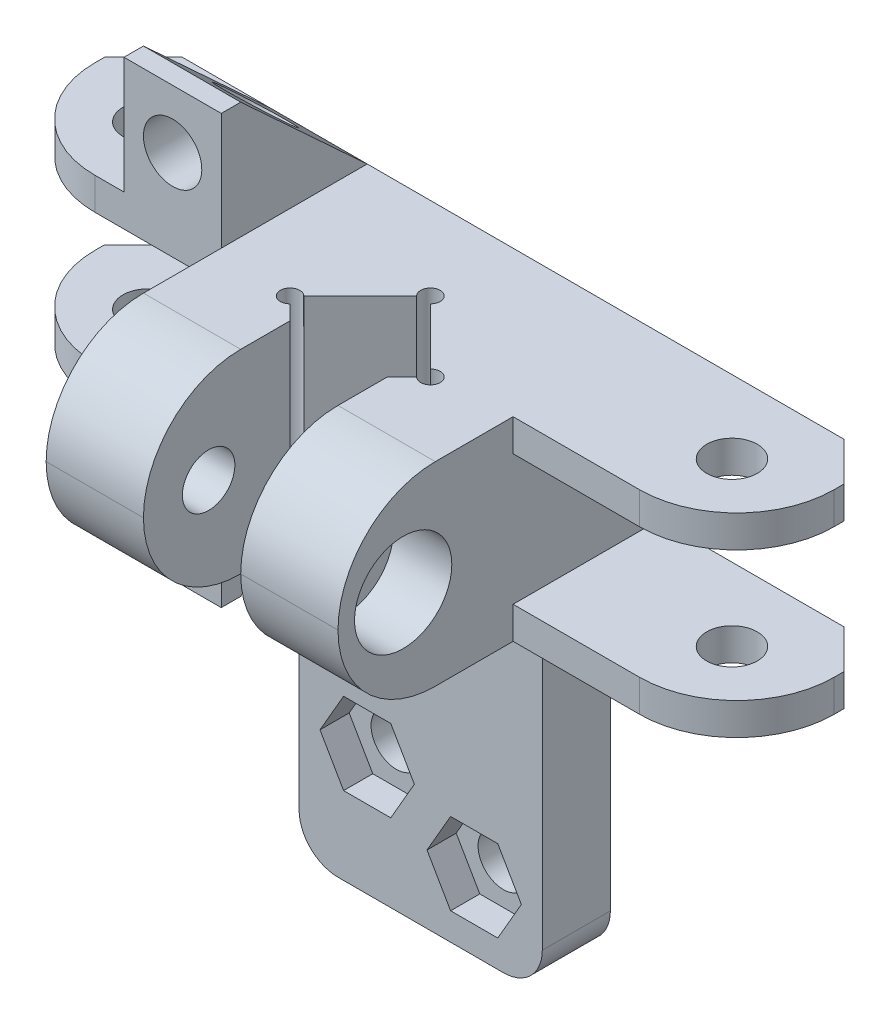
SolidWorks part; units mm, degrees
ref_plane "Ebene vorne" through (0, 0, 0) normal (0, 0, 1) x (1, 0, 0)
ref_plane "Ebene oben" through (0, 0, 0) normal (0, 1, 0) x (1, 0, 0)
ref_plane "Ebene rechts" through (0, 0, 0) normal (1, 0, 0) x (0, 0, -1)
sketch "Skizze1" plane through (0, 0, 0) normal (0, 1, 0) x (1, 0, 0)
  line L0 (-30, 5.945) -> (30, 5.945) construction
  line L1 (0, -6) -> (-30, -6) construction
  line L3 (46.7253, 15.715) -> (-46.7253, 15.715) construction
  line L4 (46.7253, 15.715) -> (46.7253, 35.715) construction
  line L5 (46.7253, 35.715) -> (-46.7253, 35.715) construction
  line L6 (-46.7253, 15.715) -> (-46.7253, 35.715) construction
  circle A0 centre (0, 0) radius 6 construction
  circle A1 centre (30, 5.945) radius 11.945 construction
  circle A2 centre (-30, 5.945) radius 11.945 construction
  circle A3 centre (0, 45.485) radius 11.945 construction
  point P7 (0, 5.945)
  point P14 (0, 15.715)
  point P17 (6, 0)
  point P18 (18.055, 5.945)
  dimension "D1" = 12
  dimension "D2" = 23.89
  dimension "D3" = 60
  dimension "D4" = 9.77
  dimension "D5" = 20
  dimension "D6" = 9.77
sketch "Skizze2" plane through (0, 0, 0) normal (0, 1, 0) x (1, 0, 0)
  line L0 (38, 13.445) -> (-38, 13.445)
  line L1 (-38, 13.445) -> (-38, -1.555)
  line L2 (-38, -1.555) -> (-15, -1.555)
  line L3 (-15, -1.555) -> (-15, -19.555)
  line L4 (-15, -19.555) -> (15, -19.555)
  line L5 (15, -19.555) -> (15, -1.555)
  line L6 (15, -1.555) -> (38, -1.555)
  line L7 (38, -1.555) -> (38, 13.445)
  line L8 (0, 13.445) -> (0, -19.555) construction
  line L9 (-30, 5.945) -> (30, 5.945) construction
  line L11 (0, -9.48) -> (7.2125, -2.2675)
  line L12 (0, -9.48) -> (-7.2125, -2.2675)
  line L13 (-7.2125, -2.2675) -> (0, 4.945)
  line L14 (7.2125, -2.2675) -> (0, 4.945)
  circle A0 centre (-30, 5.945) radius 2.6
  circle A1 centre (30, 5.945) radius 2.6
  circle A2 centre (0, 0) radius 6.1 construction
  circle A3 centre (0, 0) radius 6 construction
  point P21 (38, 5.945)
  dimension "D1" = 5.2
  dimension "D2" = 0.1
  dimension "D3" = 15
  dimension "D4" = 8
  dimension "D5" = 18
  dimension "D6" = 30
  dimension "D7" = 10.2
  dimension "D8" = 1
extrude "Aufsatz-Linear austragen1" add sketch "Skizze2" along normal mid plane 20
sketch "Skizze3" plane through (0, 0, 0) normal (0, 1, 0) x (1, 0, 0)
  line L1 (-5, -4.48) -> (5, -4.48)
  line L2 (-5, -4.48) -> (-5, -27.1109)
  line L3 (-5, -27.1109) -> (5, -27.1109)
  line L4 (5, -4.48) -> (5, -27.1109)
  line L5 (0, -9.48) -> (-7.2125, -2.2675) construction
  line L6 (0, -9.48) -> (7.2125, -2.2675) construction
  circle A0 centre (0, 4.945) radius 1
  circle A1 centre (-7.2125, -2.2675) radius 1
  circle A2 centre (7.2125, -2.2675) radius 1
  dimension "D2" = 2
  dimension "D1" = 10
extrude "Schnitt-Linear austragen1" cut sketch "Skizze3" against normal through all and the other way through all
sketch "Skizze4" plane through (0, 0, 0) normal (0, 0, 1) x (1, 0, 0)
  line L0 (42.3418, 0) -> (-42.3418, 0) construction
  line L1 (15, 6.7) -> (45, 6.7)
  line L2 (15, 6.7) -> (15, -6.7)
  line L3 (15, -6.7) -> (45, -6.7)
  line L4 (45, 6.7) -> (45, -6.7)
  line L5 (15, 10) -> (15, -10) construction
  point P4 (15, 0)
  point P7 (30, -6.7)
  dimension "D1" = 13.4
extrude "Schnitt-Linear austragen2" cut sketch "Skizze4" against normal through all and the other way through all
mirror "Spiegeln1" about plane through (0, 0, 0) normal (1, 0, 0) of "Schnitt-Linear austragen2"
sketch "Skizze5" plane through (0, 0, 0) normal (1, 0, 0) x (0, 0, -1)
  line L0 (42.3418, 0) -> (-42.3418, 0) construction
  line L1 (13.445, 0) -> (-19.555, 0) construction
  circle A0 centre (-12.855, 0) radius 2.7
  point P5 (-15.555, 0)
  dimension "D1" = 5.4
  dimension "D2" = 4
extrude "Schnitt-Linear austragen3" cut sketch "Skizze5" against normal through all and the other way through all
sketch "Skizze6" plane through (0, 0, 0) normal (1, 0, 0) x (0, 0, -1)
  circle A0 centre (-12.855, 0) radius 5
  dimension "D1" = 10
extrude "Schnitt-Linear austragen4" cut sketch "Skizze6" against normal blind 6 from vertex starting at point (15, 10, 19.555)
sketch "Skizze7" plane through (0, 0, 0) normal (1, 0, 0) x (0, 0, -1)
  line L1 (-15.2799, 4.2) -> (-17.7047, 0)
  line L2 (-17.7047, 0) -> (-15.2799, -4.2)
  line L3 (-15.2799, -4.2) -> (-10.4301, -4.2)
  line L4 (-10.4301, -4.2) -> (-8.0053, 0)
  line L5 (-8.0053, 0) -> (-10.4301, 4.2)
  line L6 (-10.4301, 4.2) -> (-15.2799, 4.2)
  circle A0 centre (-12.855, 0) radius 4.2 construction
  dimension "D1" = 8.4
extrude "Schnitt-Linear austragen5" cut sketch "Skizze7" along normal blind 6 from vertex starting at point (-15, 10, 19.555)
sketch "Skizze9" plane through (0, 0, 0) normal (1, 0, 0) x (0, 0, -1)
  line L0 (-1.555, -10) -> (13.445, -10)
  line L1 (13.445, -10) -> (0.445, -22)
  line L2 (0.445, -22) -> (-1.555, -22)
  line L3 (-1.555, -22) -> (-1.555, -10)
  dimension "D1" = 12
  dimension "D2" = 2
extrude "Aufsatz-Linear austragen2" add sketch "Skizze9" against normal blind 10 from vertex starting at point (-15, -10, 1.555)
mirror "Spiegeln2" about plane through (0, 0, 0) normal (0, 1, 0) of "Aufsatz-Linear austragen2"
sketch "Skizze10" plane through (0, 0, 0) normal (0, 0, 1) x (1, 0, 0)
  line L0 (42.3418, 0) -> (-42.3418, 0) construction
  circle A0 centre (-20, -16) radius 3
  dimension "D3" = 6
  dimension "D1" = 16
  dimension "D2" = 20
extrude "Schnitt-Linear austragen6" cut sketch "Skizze10" against normal through all and the other way through all
mirror "Spiegeln3" about plane through (0, 0, 0) normal (0, 1, 0) of "Schnitt-Linear austragen6"
chamfer "Fase1" distance 4 angle 45 4 edges at (-38, 8.35, -13.445) (-38, -8.35, -13.445) (38, 8.35, -13.445) (38, -8.35, -13.445)
fillet "Verrundung1" radius 10 3 edges at (38, 8.35, 1.555) (38, -8.35, 1.555) (-38, -8.35, 1.555)
fillet "Verrundung2" radius 10 4 edges at (10, -10, 19.555) (-10, -10, 19.555) (-10, 10, 19.555) (10, 10, 19.555)
sketch "Skizze11" plane through (0, 0, -13.445) normal (0, 0, -1) x (-1, 0, 0)
  line L0 (10, -10) -> (15, -10)
  line L1 (-34, -10) -> (15, -10) construction
  line L2 (10, -10) -> (-10, -10)
  line L3 (8, -38.4) -> (-3, -38.4) construction
  line L4 (15, -48) -> (-10, -48)
  line L5 (-10, -10) -> (-10, -48)
  line L6 (0, 38.5) -> (0, -38.5) construction
  line L7 (15, -10) -> (15, -48)
  circle A0 centre (-3, -41) radius 2.6
  circle A1 centre (8, -35.8) radius 2.6
  point P0 (0, -10)
  dimension "D5" = 5.2
  dimension "D2" = 7
  dimension "D3" = 7
  dimension "D1" = 10
  dimension "D4" = 31
  dimension "D6" = 7
extrude "Aufsatz-Linear austragen3" add sketch "Skizze11" against normal blind 7
fillet "Verrundung3" radius 4 2 edges at (10, -48, -9.945) (-15, -48, -9.945)
sketch "Skizze12" plane through (0, 0, -6.445) normal (0, 0, 1) x (1, 0, 0)
  line L1 (5.4249, -36.8) -> (0.5751, -36.8)
  line L2 (0.5751, -36.8) -> (-1.8497, -41)
  line L3 (-1.8497, -41) -> (0.5751, -45.2)
  line L4 (0.5751, -45.2) -> (5.4249, -45.2)
  line L5 (5.4249, -45.2) -> (7.8497, -41)
  line L6 (7.8497, -41) -> (5.4249, -36.8)
  line L7 (-10.4249, -40) -> (-5.5751, -40)
  line L8 (-5.5751, -40) -> (-3.1503, -35.8)
  line L9 (-3.1503, -35.8) -> (-5.5751, -31.6)
  line L10 (-5.5751, -31.6) -> (-10.4249, -31.6)
  line L11 (-10.4249, -31.6) -> (-12.8497, -35.8)
  line L12 (-12.8497, -35.8) -> (-10.4249, -40)
  circle A0 centre (3, -41) radius 4.2 construction
  circle A1 centre (-8, -35.8) radius 4.2 construction
  dimension "D1" = 8.4
extrude "Schnitt-Linear austragen7" cut sketch "Skizze12" against normal blind 3
equation "\"D6@Skizze1\" = \"D4@Skizze1\""
